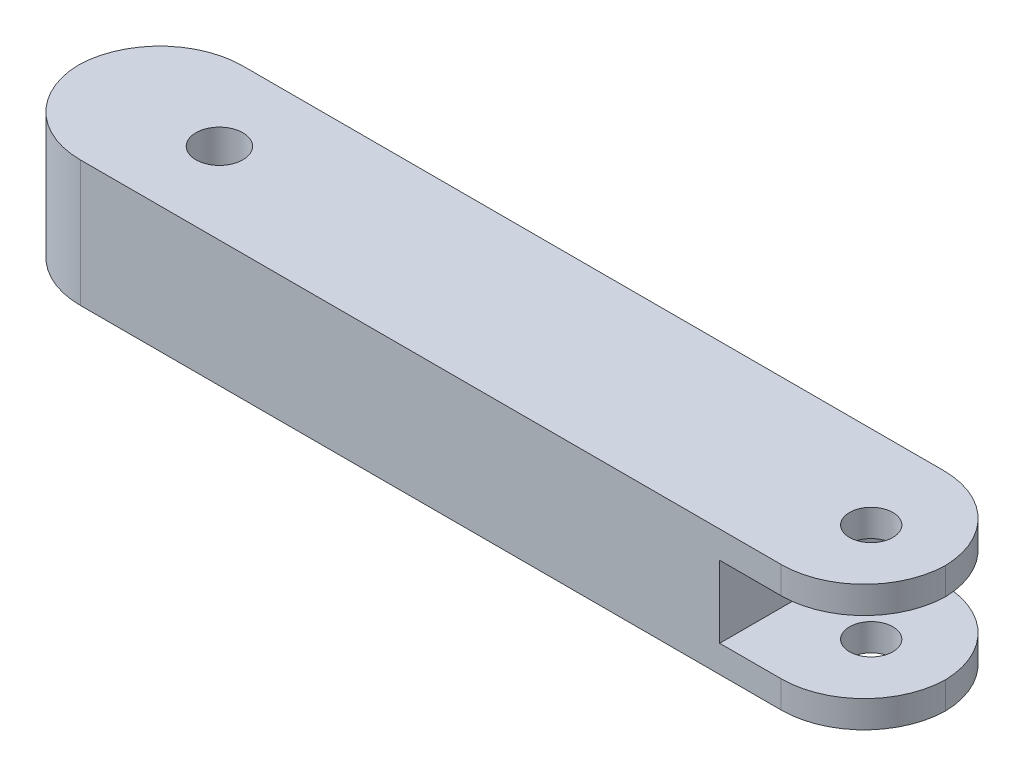
SolidWorks part; units mm, degrees
material "Balsa"
ref_plane "Front Plane" through (0, 0, 0) normal (0, 0, 1) x (1, 0, 0)
ref_plane "Top Plane" through (0, 0, 0) normal (0, 1, 0) x (1, 0, 0)
ref_plane "Right Plane" through (0, 0, 0) normal (1, 0, 0) x (0, 0, -1)
sketch "Sketch1" plane through (0, 0, 0) normal (0, 1, 0) x (1, 0, 0)
  line L1 (-95.3862, -36.8675) -> (144.6138, -36.8675)
  line L2 (-95.3862, -36.8675) -> (-95.3862, 8.1325)
  line L3 (-95.3862, 8.1325) -> (144.6138, 8.1325)
  line L4 (144.6138, -36.8675) -> (144.6138, 8.1325)
  dimension "D1" = 240
  dimension "D2" = 45
extrude "Boss-Extrude1" add sketch "Sketch1" along normal blind 34.9
fillet "Fillet1" radius 23 4 edges at (-95.3862, 17.45, 36.8675) (-95.3862, 17.45, -8.1325) (144.6138, 17.45, 36.8675) (144.6138, 17.45, -8.1325)
sketch "Sketch2" plane through (0, 34.9, 0) normal (0, 1, 0) x (1, 0, 0)
  line L0 (121.6138, 8.1325) -> (-72.3862, 8.1325) construction
  line L1 (104.6084, 8.1325) -> (154.1732, 8.1325)
  line L2 (104.6084, 8.1325) -> (104.6084, -36.8797)
  line L3 (104.6084, -36.8797) -> (154.1732, -36.8797)
  line L4 (154.1732, 8.1325) -> (154.1732, -36.8797)
  dimension "D1" = 40
extrude "Cut-Extrude1" cut sketch "Sketch2" against normal blind 19.9 from offset 7.5 offset against normal yes
sketch "Sketch3" plane through (0, 0, 0) normal (0, -1, 0) x (1, 0, 0)
  circle A0 centre (124.6084, 14.935) radius 6
  dimension "D1" = 12
  dimension "D2" = 20
extrude "Cut-Extrude2" cut sketch "Sketch3" against normal through all
sketch "Sketch4" plane through (0, 0, 0) normal (0, -1, 0) x (1, 0, 0)
  circle A0 centre (-56.3807, 14.3675) radius 6.5
  dimension "D1" = 13
  dimension "D2" = 39
extrude "Cut-Extrude3" cut sketch "Sketch4" against normal through all
scale "Scale1" bodies to scale 104 scale about origin uniform scaling yes scale factor 0.31
